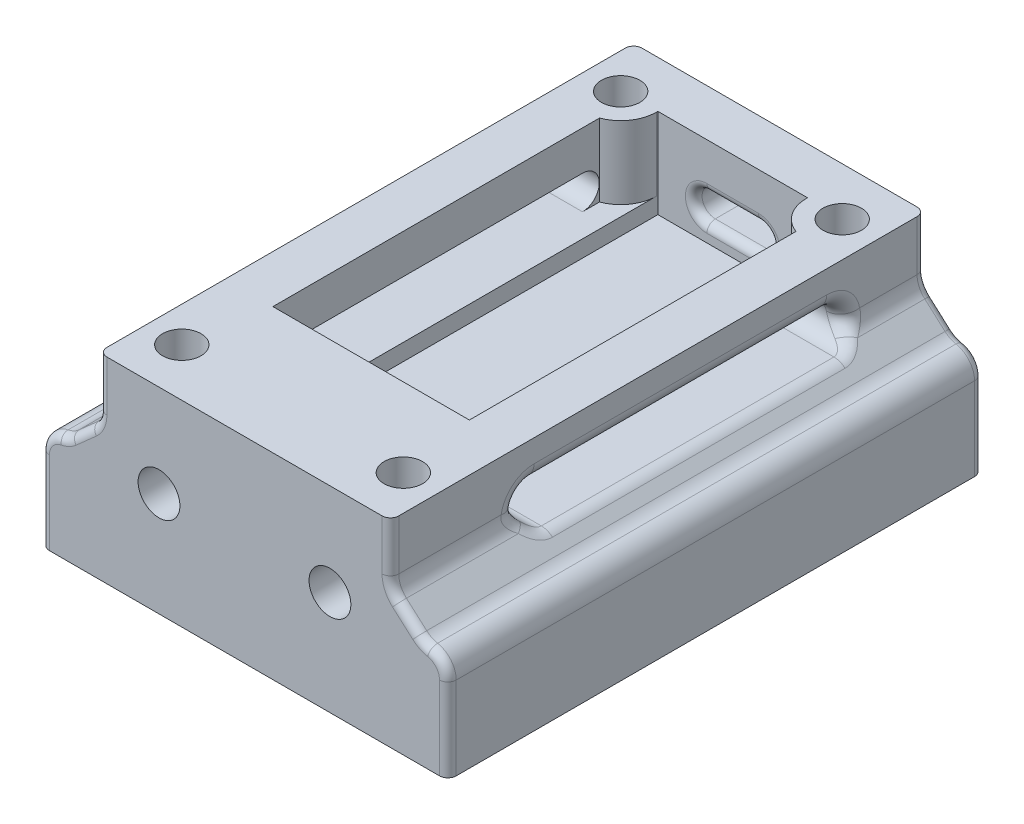
SolidWorks part; units mm, degrees
ref_plane "Front Plane" through (0, 0, 0) normal (0, 0, 1) x (1, 0, 0)
ref_plane "Top Plane" through (0, 0, 0) normal (0, 1, 0) x (1, 0, 0)
ref_plane "Right Plane" through (0, 0, 0) normal (1, 0, 0) x (0, 0, -1)
sketch "Sketch1" plane through (0, 0, 0) normal (0, 1, 0) x (1, 0, 0)
  line L1 (24.33, -32) -> (-24.33, -32)
  line L2 (24.33, -32) -> (24.33, 32)
  line L3 (24.33, 32) -> (-24.33, 32)
  line L4 (-24.33, -32) -> (-24.33, 32)
  line L5 (0, 32) -> (0, -32) construction
  line L6 (24.33, 0) -> (-24.33, 0) construction
  point P0 (0, 0)
  dimension "D1" = 48.66
  dimension "D2" = 64
extrude "Boss-Extrude1" add sketch "Sketch1" along normal blind 23.5
sketch "Sketch2" plane through (0, 23.5, 0) normal (0, 1, 0) x (1, 0, 0)
  line L0 (0, 32) -> (0, -32) construction
  line L1 (24.33, 32) -> (-24.33, 32) construction
  line L2 (-24.33, -32) -> (24.33, -32) construction
  line L3 (-24.33, 0) -> (24.33, 0) construction
  line L4 (-24.33, 32) -> (-24.33, -32) construction
  line L5 (24.33, -32) -> (24.33, 32) construction
  line L7 (-11.75, -16.85) -> (11.75, -16.85)
  line L8 (-11.75, -16.85) -> (-11.75, 22.2201)
  line L9 (-8.9526, 26.4) -> (8.9526, 26.4)
  line L10 (11.75, -16.85) -> (11.75, 22.2201)
  line L11 (0, 26.4) -> (0, -16.85) construction
  line L12 (-11.75, 0) -> (11.75, 0) construction
  line L13 (-8.95, -16.85) -> (8.95, -16.85)
  line L14 (-8.95, -16.85) -> (-8.95, 31.4)
  line L15 (-8.95, 31.4) -> (8.95, 31.4)
  line L16 (8.95, -16.85) -> (8.95, 31.4)
  line L17 (0, 32) -> (0, -16.85) construction
  line L18 (-8.88, 0) -> (8.88, 0) construction
  circle A2 centre (-13.25, -26.25) radius 2.3
  circle A11 centre (-13.25, 26.25) radius 2.3
  circle A12 centre (13.25, 26.25) radius 2.3
  circle A13 centre (13.25, -26.25) radius 2.3
  arc A14 (-8.9526, 26.4) -> (-11.75, 22.2201) centre (-13.25, 26.25) cw
  arc A15 (8.9526, 26.4) -> (11.75, 22.2201) centre (13.25, 26.25) ccw
  circle A16 centre (-13.25, -26.25) radius 4.3
  circle A17 centre (13.25, -26.25) radius 4.3
  circle A18 centre (-13.25, 26.25) radius 4.3 construction
  circle A19 centre (13.25, 26.25) radius 4.3 construction
  point P32 (0, 0)
  point P36 (0, 0)
  dimension "D1" = 5.75
  dimension "D5" = 13.25
  dimension "D10" = 48.25
  dimension "D2" = 26.5
  dimension "D3" = 52.5
  dimension "D4" = 2
  dimension "D6" = 5.75
  dimension "D8" = 23.5
  dimension "D9" = 43.25
  dimension "D7" = 17.9
  dimension "D11" = 5.6
extrude "Cut-Extrude1" cut sketch "Sketch2" against normal blind 8.7 contours L14 A14 L8 L7 | L7 L16 L9 L14 | A15 L16 L7 L10 region at (-10.3324, 23.5, -3.2452) region at (0, 23.5, -4.775) region at (10.3324, 23.5, -3.2452)
extrude "Cut-Extrude2" cut sketch "Sketch2<4>" against normal blind 10.7 contours L7 L16 L9 L14 region at (0, 23.5, -4.775)
sketch "Sketch2<4>" plane through (0, 23.5, 0) normal (0, 1, 0) x (1, 0, 0) same geometry as "Sketch2"
sketch "Sketch3" plane through (0, 0, -26.4) normal (0, 0, 1) x (1, 0, 0)
  line L0 (0, 12.8) -> (0, 23.5) construction
  line L1 (-8.95, 12.8) -> (8.95, 12.8) construction
  line L2 (-8.95, 23.5) -> (8.95, 23.5) construction
  line L3 (-3.0833, 16.3779) -> (3.0833, 16.3779) construction
  line L4 (-3.0833, 17.9559) -> (3.0833, 17.9559)
  line L5 (-3.0833, 14.8) -> (3.0833, 14.8)
  line L6 (-8.95, 12.8) -> (-8.95, 23.5) construction
  arc A0 (-3.0833, 17.9559) -> (-3.0833, 14.8) centre (-3.0833, 16.3779) ccw
  arc A1 (3.0833, 14.8) -> (3.0833, 17.9559) centre (3.0833, 16.3779) ccw
  point P8 (0, 16.3779)
  dimension "D2" = 1.5779
  dimension "D1" = 2
  dimension "D3" = 5.8667
extrude "Cut-Extrude3" cut sketch "Sketch3" against normal through all
sketch "Sketch4" plane through (-11.75, 0, 0) normal (1, 0, 0) x (0, 0, -1)
  line L0 (2.6851, 14.8) -> (2.6851, 23.5) construction
  line L1 (-16.85, 14.8) -> (22.2201, 14.8) construction
  line L2 (-16.85, 23.5) -> (22.2201, 23.5) construction
  line L3 (20.1851, 16.8) -> (-14.8149, 16.8) construction
  line L5 (20.1851, 14.8) -> (-14.8149, 14.8)
  line L6 (20.1851, 18.8) -> (-14.8149, 18.8)
  arc A0 (20.1851, 14.8) -> (20.1851, 18.8) centre (20.1851, 16.8) ccw
  arc A1 (-14.8149, 18.8) -> (-14.8149, 14.8) centre (-14.8149, 16.8) ccw
  point P10 (2.6851, 16.8)
  point P15 (2.6851, 14.8)
  dimension "D1" = 4
  dimension "D2" = 39
sketch "Sketch5" plane through (11.75, 0, 0) normal (-1, 0, 0) x (0, 0, 1)
  line L0 (-2.6851, 14.8) -> (-2.6851, 23.5) construction
  line L1 (16.85, 14.8) -> (-22.2201, 14.8) construction
  line L2 (16.85, 23.5) -> (-22.2201, 23.5) construction
  line L3 (14.8149, 16.8) -> (-20.1851, 16.8) construction
  line L4 (14.8149, 14.8) -> (-20.1851, 14.8)
  line L5 (14.8149, 18.8) -> (-20.1851, 18.8)
  arc A0 (14.8149, 14.8) -> (14.8149, 18.8) centre (14.8149, 16.8) ccw
  arc A1 (-20.1851, 18.8) -> (-20.1851, 14.8) centre (-20.1851, 16.8) ccw
  point P8 (-2.6851, 16.8)
  point P13 (-2.6851, 14.8)
  dimension "D1" = 4
  dimension "D2" = 39
extrude "Cut-Extrude4" cut sketch "Sketch4" against normal through all
extrude "Cut-Extrude5" cut sketch "Sketch5" against normal through all
sketch "Sketch6" plane through (0, 0, 0) normal (0, -1, 0) x (1, 0, 0)
  line L0 (0, 32) -> (0, -32) construction
  line L1 (-24.33, 32) -> (24.33, 32) construction
  line L2 (24.33, -32) -> (-24.33, -32) construction
  line L3 (24.33, 0) -> (-24.33, 0) construction
  line L4 (24.33, 32) -> (24.33, -32) construction
  line L5 (-24.33, -32) -> (-24.33, 32) construction
  line L7 (-18, -26) -> (18, -26)
  line L8 (-18, -26) -> (-18, 26)
  line L9 (-18, 26) -> (18, 26)
  line L10 (18, -26) -> (18, 26)
  line L11 (0, 26) -> (0, -26) construction
  line L12 (-18, 0) -> (18, 0) construction
  point P12 (0, 0)
  dimension "D1" = 36
  dimension "D2" = 52
extrude "Cut-Extrude6" cut sketch "Sketch6" against normal blind 9.9
sketch "Sketch7" plane through (0, 0, 0) normal (0, -1, 0) x (1, 0, 0)
  line L0 (-24.33, 0) -> (24.33, 0) construction
  line L1 (-24.33, -32) -> (-24.33, 32) construction
  line L2 (24.33, 32) -> (24.33, -32) construction
  line L3 (0, 32) -> (0, -32) construction
  line L4 (-24.33, 32) -> (24.33, 32) construction
  line L5 (24.33, -32) -> (-24.33, -32) construction
  circle A0 centre (-20.33, -28) radius 2.3
  circle A1 centre (-20.33, 28) radius 2.3
  circle A2 centre (20.33, -28) radius 2.3
  circle A3 centre (20.33, 28) radius 2.3
  dimension "D1" = 4
  dimension "D2" = 4
extrude "Cut-Extrude7" cut sketch "Sketch7" against normal blind 9 contours A0 | A2 | A3 | A1
extrude "Cut-Extrude8" cut sketch "Sketch2<5>" against normal blind 7.5 contours A12 | A11 | A2 | A13 region at (-13.25, 23.5, 26.25) region at (-13.25, 23.5, -26.25) region at (13.25, 23.5, -26.25) region at (13.25, 23.5, 26.25)
sketch "Sketch2<5>" plane through (0, 23.5, 0) normal (0, 1, 0) x (1, 0, 0) same geometry as "Sketch2"
sketch "Sketch8" plane through (0, 0, 32) normal (0, 0, 1) x (1, 0, 0)
  line L0 (0, 0) -> (0, 23.5) construction
  line L1 (-24.33, 23.5) -> (24.33, 23.5) construction
  line L2 (-24.33, 11.75) -> (24.33, 11.75) construction
  line L3 (-24.33, 23.5) -> (-24.33, 0) construction
  line L4 (24.33, 23.5) -> (24.33, 0) construction
  line L5 (-20.7983, 13.2754) -> (-18.3771, 15.4296)
  line L10 (0, 23.5) -> (0, 12.58) construction
  line L11 (-17.455, 11.75) -> (17.455, 11.75) construction
  line L12 (-22.6263, 12.58) -> (-24.33, 12.58)
  line L13 (-17.455, 17.4842) -> (-17.455, 23.5)
  line L14 (-17.455, 23.5) -> (-24.33, 23.5)
  line L15 (-24.33, 12.58) -> (-24.33, 23.5)
  line L17 (20.7983, 13.2754) -> (18.3771, 15.4296)
  line L18 (17.455, 17.4842) -> (17.455, 23.5)
  line L19 (17.455, 23.5) -> (24.33, 23.5)
  line L20 (24.33, 12.58) -> (24.33, 23.5)
  line L21 (22.6263, 12.58) -> (24.33, 12.58)
  arc A0 (-18.3771, 15.4296) -> (-17.455, 17.4842) centre (-20.205, 17.4842) ccw
  arc A1 (-20.7983, 13.2754) -> (-22.6263, 12.58) centre (-22.6263, 15.33) cw
  arc A2 (20.7983, 13.2754) -> (22.6263, 12.58) centre (22.6263, 15.33) ccw
  arc A3 (18.3771, 15.4296) -> (17.455, 17.4842) centre (20.205, 17.4842) cw
  point P11 (0, 11.75)
  point P24 (-17.455, 16.25)
  point P27 (-21.58, 12.58)
  point P30 (21.58, 12.58)
  point P33 (17.455, 16.25)
  dimension "D2" = 2.75
  dimension "D6" = 2.75
  dimension "D1" = 6.875
  dimension "D3" = 7.25
  dimension "D4" = 2.75
  dimension "D5" = 10.92
extrude "Cut-Extrude9" cut sketch "Sketch8" against normal through all
sketch "Sketch10" plane through (0, 0, -32) normal (0, 0, -1) x (-1, 0, 0)
  line L0 (0, 23.5) -> (0, 0) construction
  line L1 (-17.455, 23.5) -> (17.455, 23.5) construction
  line L2 (-24.33, 7) -> (24.33, 7) construction
  line L3 (-24.33, 12.58) -> (-24.33, 0) construction
  line L4 (24.33, 12.58) -> (24.33, 0) construction
  line L5 (-24.33, 0) -> (24.33, 0) construction
  line L6 (18, 9.9) -> (-18, 9.9) construction
  line L7 (-3, 9.9) -> (3, 9.9)
  line L8 (-3, 9.9) -> (-3, 3.9)
  line L9 (-3, 3.9) -> (3, 3.9)
  line L10 (3, 9.9) -> (3, 3.9)
  line L11 (0, 3.9) -> (0, 9.9) construction
  line L12 (-3, 6.9) -> (3, 6.9) construction
  point P13 (0, 7)
  dimension "D1" = 7
  dimension "D2" = 6
  dimension "D3" = 6
extrude "Cut-Extrude10" cut sketch "Sketch10" against normal up to next
sketch "Sketch11" plane through (0, 0, 32) normal (0, 0, 1) x (1, 0, 0)
  line L0 (0, 0) -> (0, 23.5) construction
  line L1 (-17.455, 23.5) -> (17.455, 23.5) construction
  line L2 (-24.33, 0) -> (24.33, 0) construction
  line L11 (0, 24.2) -> (0, -0.7) construction
  line L12 (-10.225, 12.45) -> (10.225, 12.45) construction
  circle A1 centre (-10.225, 12.45) radius 2.5
  circle A2 centre (10.225, 12.45) radius 2.5
  dimension "D2" = 12.45
  dimension "D1" = 20.45
extrude "Cut-Extrude11" cut sketch "Sketch11" against normal blind 6.1
fillet "Fillet1" radius 2.75 1 edges at (24.33, 12.58, 0)
fillet "Fillet2" radius 2 16 edges at (18.9003, 14.9641, -20.9786) (17.6116, 16.5695, -22.1717) (17.455, 18.4383, -21.3321) (17.455, 18.8, -2.6851) (17.455, 18.4383, 15.962) (17.6795, 16.3958, 16.7737) (18.9003, 14.9641, 15.6084) (-18.9003, 14.9641, 15.6084) (-17.6116, 16.5695, 16.8016) (-17.455, 18.4383, 15.962) (-17.455, 18.8, -2.6851) (-17.455, 18.4383, -21.3321) (-17.6795, 16.3958, -22.1438) (-18.9003, 14.9641, -20.9786) (19.0848, 14.8, -2.6851) (-19.0848, 14.8, -2.6851)
fillet "Fillet3" radius 2.75 1 edges at (-24.33, 12.58, 0)
fillet "Fillet4" radius 1 24 edges at (-24.33, 4.9652, 32) (-19.5877, 14.3525, 32) (-23.7015, 11.6803, 32) (-17.455, 20.4921, 32) (-17.6961, 16.3582, 32) (-21.4073, 12.8649, 32) (17.455, 20.4921, 32) (17.6961, 16.3582, 32) (19.5877, 14.3525, 32) (21.4073, 12.8649, 32) (23.7015, 11.6803, 32) (24.33, 4.9652, 32) (17.6961, 16.3582, -32) (17.455, 20.4921, -32) (19.5877, 14.3525, -32) (21.4073, 12.8649, -32) (24.33, 4.9652, -32) (23.7015, 11.6803, -32) (-17.455, 20.4921, -32) (-17.6961, 16.3582, -32) (-19.5877, 14.3525, -32) (-21.4073, 12.8649, -32) (-23.7015, 11.6803, -32) (-24.33, 4.9652, -32)
fillet "Fillet5" radius 1 8 edges at (-3, 6.9, -32) (0, 3.9, -32) (3, 6.9, -32) (0, 9.9, -32) (-4.6612, 16.3779, -32) (0, 14.8, -32) (4.6612, 16.3779, -32) (0, 17.9559, -32)
fillet "Fillet6" radius 1 4 edges at (4.6612, 16.3779, -26.4) (0, 14.8, -26.4) (-4.6612, 16.3779, -26.4) (0, 17.9559, -26.4)
